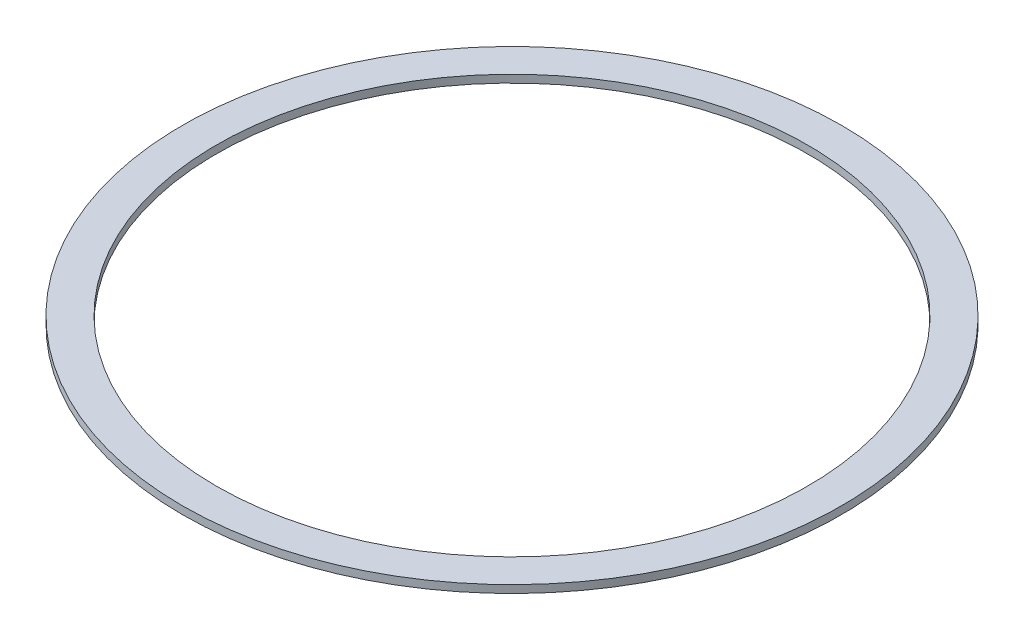
SolidWorks part; units mm, degrees
material "Acetal White"
ref_plane "Front Plane" through (0, 0, 0) normal (0, 0, 1) x (1, 0, 0)
ref_plane "Top Plane" through (0, 0, 0) normal (0, 1, 0) x (1, 0, 0)
ref_plane "Right Plane" through (0, 0, 0) normal (1, 0, 0) x (0, 0, -1)
ref_axis "Axis1" through (0, -55, 0) along (0, 1, 0)
sketch "Sketch1" plane through (0, 0, 0) normal (0, 1, 0) x (1, 0, 0)
  circle A0 centre (0, 0) radius 135.75
  circle A1 centre (0, 0) radius 121.75
  dimension "D1" = 271.5
  dimension "D2" = 243.5
extrude "Boss-Extrude1" add sketch "Sketch1" along normal blind 3.175
